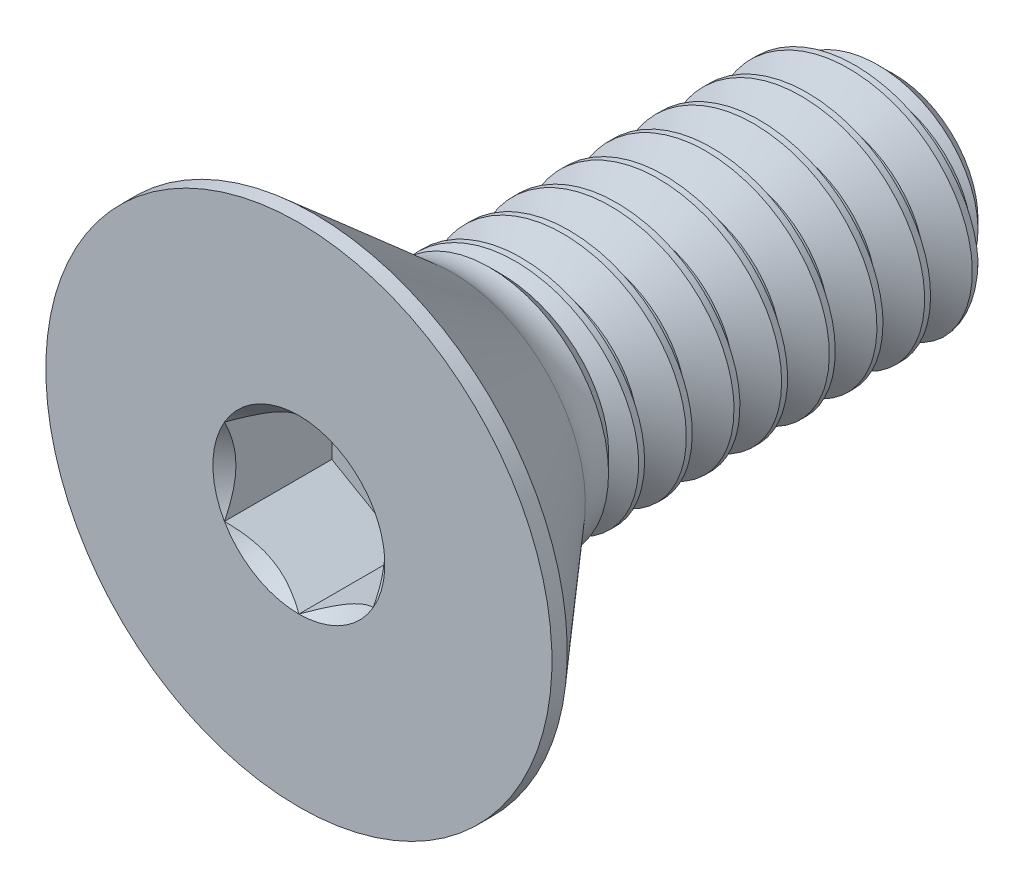
SolidWorks part; units mm, degrees
ref_plane "Front" through (0, 0, 0) normal (0, 0, 1) x (1, 0, 0)
ref_plane "Top" through (0, 0, 0) normal (0, 1, 0) x (1, 0, 0)
ref_plane "Right" through (0, 0, 0) normal (1, 0, 0) x (0, 0, -1)
sketch "Sketch1" plane through (0, 0, 0) normal (1, 0, 0) x (0, 0, -1)
  line L0 (0, 6.7437) -> (0.4089, 6.7437) construction
  line L1 (0.4089, 6.7437) -> (4.0894, 3.5443) construction
  line L2 (0, 3.175) -> (15.875, 3.175)
  line L3 (15.875, 3.175) -> (15.875, 0)
  line L4 (15.875, 0) -> (0, 0)
  line L5 (0, 0) -> (0, 6.7437) construction
  line L6 (0, 6.7437) -> (0, -6.7437) construction
  line L7 (15.875, 3.175) -> (15.875, -3.175) construction
  line L8 (0, -6.7437) -> (0.4089, -6.7437) construction
  line L9 (0.4089, -6.7437) -> (4.0894, -3.5443) construction
  line L11 (0, 3.175) -> (0, 0)
  line L12 (5.0772, 3.175) -> (5.0772, 0) construction
  arc A1 (4.0894, 3.5443) -> (5.0772, 3.175) centre (5.0772, 4.6807) ccw construction
  dimension "D1" = 0.4089
  dimension "Head Ht" = 4.0894
  dimension "Head Dia" = 13.4874
  dimension "Dia" = 6.35
  dimension "Lg" = 15.875
  dimension "Head Angle" = 82
revolve "Revolve1" add sketch "Sketch1" angle 360 mid plane about L4
sketch "Sketch3" plane through (0, 0, -15.875) normal (0, 0, -1) x (-1, 0, 0)
  circle A0 centre (0, 0) radius 3.175
curve "Helix/Spiral1" pitch 1.27 height 15.875 radius 3.175 centre (0, 0, -15.875) axis (0, 0, 1) start towards (0, 1, 0)
sketch "Sketch2" plane through (0, 0, 0) normal (1, 0, 0) x (0, 0, -1)
  line L0 (15.875, 3.175) -> (16.9862, 3.175)
  line L1 (16.9862, 3.175) -> (16.51, 2.3501)
  line L2 (16.51, 2.3501) -> (16.3512, 2.3501)
  line L3 (16.3512, 2.3501) -> (15.875, 3.175)
  line L4 (16.1131, 2.7626) -> (16.7481, 2.7626) construction
  dimension "D1" = 60
  dimension "D2" = 0.1588
  dimension "D3" = 0.635
chamfer "Chamfer1" distance 0.9525 angle 45 1 edges at (0, 3.175, -15.875)
sweep "Cut-Sweep1" cut profiles "Sketch2" path "Helix/Spiral1" align with end faces yes
sketch "Sketch7" plane through (0, 0, 0) normal (1, 0, 0) x (0, 0, -1)
  line L0 (0, 6.7437) -> (0.4089, 6.7437) construction
  line L1 (0.4089, 6.7437) -> (4.0894, 3.5443) construction
  line L2 (0, 6.7437) -> (0.4089, 6.7437)
  line L3 (0.4089, 6.7437) -> (4.0894, 3.5443)
  line L4 (5.0772, 3.175) -> (5.0772, 0) construction
  line L5 (5.0772, 3.175) -> (5.0772, 0)
  line L7 (0, 0) -> (0, 6.7437) construction
  line L8 (0, 0) -> (0, 6.7437)
  line L9 (0, 0) -> (5.0772, 0)
  line L10 (7.4181, 0) -> (-7.4181, 0) construction
  arc A0 (4.0894, 3.5443) -> (5.0772, 3.175) centre (5.0772, 4.6807) ccw construction
  arc A1 (4.0894, 3.5443) -> (5.0772, 3.175) centre (5.0772, 4.6807) ccw
revolve "Revolve2" add sketch "Sketch7" angle 360 mid plane about L9
ref_plane "Plane1" through (0, 0, -5.0772) normal (0, 0, 1) x (1, 0, 0)
sketch "Sketch8" plane through (0, 0, -5.0772) normal (0, 0, 1) x (1, 0, 0)
  circle A0 centre (0, 0) radius 3.175
extrude "Boss-Extrude1" add sketch "Sketch8" against normal through all draft 45
sketch "Sketch5" plane through (0, 0, 0) normal (0, 0, 1) x (1, 0, 0)
  line L1 (1.9844, -1.1457) -> (1.9844, 1.1457)
  line L2 (1.9844, 1.1457) -> (0, 2.2914)
  line L3 (0, 2.2914) -> (-1.9844, 1.1457)
  line L4 (-1.9844, 1.1457) -> (-1.9844, -1.1457)
  line L5 (-1.9844, -1.1457) -> (0, -2.2914)
  line L6 (0, -2.2914) -> (1.9844, -1.1457)
  circle A0 centre (0, 0) radius 1.9844 construction
  dimension "Hex" = 3.9688
extrude "Cut-Extrude2" cut sketch "Sketch5" against normal blind 2.8626
sketch "Sketch6" plane through (0, 0, 0) normal (0, 0, 1) x (1, 0, 0)
  circle A0 centre (0, 0) radius 2.2914
extrude "Cut-Extrude3" cut sketch "Sketch6" against normal through all draft 45
sketch "Sketch9" [suppressed] plane through (0, 0, -5.0772) normal (0, 0, 1) x (1, 0, 0)
  circle A1 centre (0, 0) radius 3.175
  circle A2 centre (0, 0) radius 3.175
  point P0 (0, 3.175)
  dimension "D1" = 0
extrude "Boss-Extrude2" [suppressed] add sketch "Sketch9" against normal offset from surface (13.9728 mm away) 22.225 up to face at (0, 2.2225, -15.875)
sketch "Sketch10" plane through (0, 0, 0) normal (1, 0, 0) x (0, 0, -1)
  line L0 (15.875, 3.175) -> (15.875, -3.175) construction
  point P0 (13.97, -3.175)
  dimension "D1" = 1.905
equation "\"D3@Helix/Spiral1\" = \"Lg@Sketch1\""
equation "\"D2@Sketch2\" = \"D4@Helix/Spiral1\" * .125"
equation "\"D3@Sketch2\" = \"D4@Helix/Spiral1\" * .5"
equation "\"D1@Chamfer1\" = \"D4@Helix/Spiral1\" * .75"
equation "\"D1@Cut-Extrude2\" = \"Head Ht@Sketch1\" * .7"
equation "\"D1@Sketch1\" = \"Head Ht@Sketch1\" * .1"
equation "\"D1@Sketch10\" = \"D4@Helix/Spiral1\" * 1.5"
